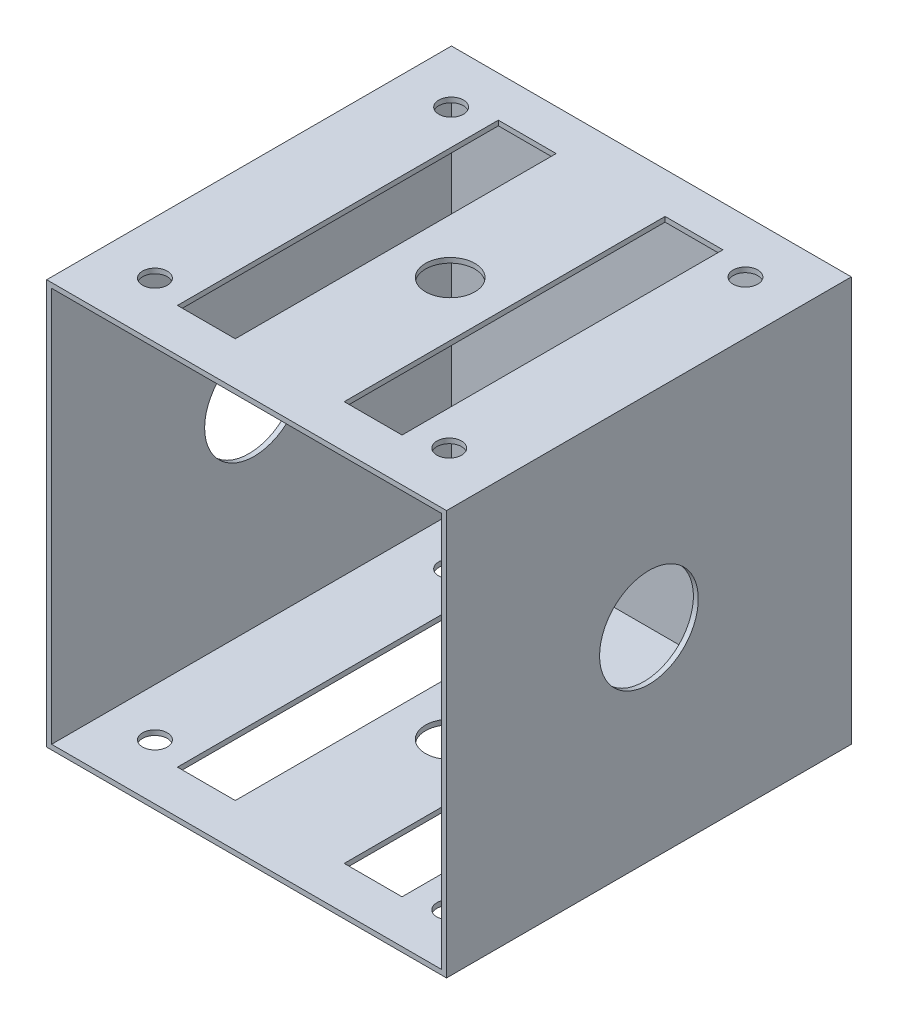
SolidWorks part; units mm, degrees
ref_plane "Front Plane" through (0, 0, 0) normal (0, 0, 1) x (1, 0, 0)
ref_plane "Top Plane" through (0, 0, 0) normal (0, 1, 0) x (1, 0, 0)
ref_plane "Right Plane" through (0, 0, 0) normal (1, 0, 0) x (0, 0, -1)
sketch "Sketch1" plane through (0, 0, 0) normal (0, 0, 1) x (1, 0, 0)
  line L1 (102.87, -104.14) -> (-102.87, -104.14)
  line L2 (102.87, -104.14) -> (102.87, 104.14)
  line L3 (102.87, 104.14) -> (-102.87, 104.14)
  line L4 (-102.87, -104.14) -> (-102.87, 104.14)
  line L5 (102.87, -104.14) -> (-102.87, 104.14) construction
  line L6 (102.87, 104.14) -> (-102.87, -104.14) construction
  point P0 (0, 0)
  dimension "D1" = 205.74
  dimension "D2" = 208.28
extrude "Boss-Extrude1" add sketch "Sketch1" along normal blind 208.28
shell "Shell1" thickness 2.54 removed face at (0, 0, 208.28)
sketch "Sketch2" plane through (0, -101.6, 0) normal (0, 1, 0) x (1, 0, 0)
  line L0 (-102.87, 0) -> (102.87, -207.063) construction
  line L3 (102.87, -208.28) -> (102.87, 0) construction
  line L4 (102.87, 0) -> (-102.87, -208.28) construction
  line L6 (75.7131, -179.7315) -> (-75.7131, -179.7315) construction
  line L7 (75.7131, -179.7315) -> (75.7131, -27.3315) construction
  line L8 (75.7131, -27.3315) -> (-75.7131, -27.3315) construction
  line L9 (-75.7131, -179.7315) -> (-75.7131, -27.3315) construction
  line L10 (75.7131, -179.7315) -> (-75.7131, -27.3315) construction
  line L11 (75.7131, -27.3315) -> (-75.7131, -179.7315) construction
  circle A0 centre (0, -103.5315) radius 12.7
  circle A1 centre (-75.7131, -27.3315) radius 6.35
  circle A2 centre (75.7131, -27.3315) radius 6.35
  circle A3 centre (75.7131, -179.7315) radius 6.35
  circle A4 centre (-75.7131, -179.7315) radius 6.35
  point P3 (102.87, -207.063)
  point P6 (102.87, 0)
  point P21 (-102.87, -208.28)
  point P23 (-102.87, 0)
  point P25 (100.33, -205.1655)
  point P26 (100.33, -208.28)
  dimension "D1" = 25.4
  dimension "D3" = 12.7
  dimension "D2" = 76.2
extrude "Cut-Extrude1" cut sketch "Sketch2" against normal through all both and the other way through all
sketch "Sketch4" plane through (0, 0, 2.54) normal (0, 0, 1) x (1, 0, 0)
  line L0 (-33.02, 0) -> (33.02, 0) construction
  circle A0 centre (0, 0) radius 2.5
  circle A1 centre (33.02, 0) radius 2.5
  circle A2 centre (-33.02, 0) radius 2.5
  point P7 (0, 0)
  point P8 (0, 0)
  point P9 (0, 0)
  point P10 (0, 0)
  point P11 (0, 0)
  dimension "D1" = 5
  dimension "D2" = 33.02
extrude "Cut-Extrude2" cut sketch "Sketch4" against normal blind 208.28
sketch "Sketch5" plane through (0, 104.14, 0) normal (0, 1, 0) x (1, 0, 0)
  line L0 (-42.9007, -103.5315) -> (0, -103.5315) construction
  line L1 (-34.3725, -179.7315) -> (-51.4288, -179.7315)
  line L2 (-34.3725, -179.7315) -> (-34.3725, -27.3315)
  line L3 (-34.3725, -27.3315) -> (-51.4288, -27.3315)
  line L4 (-51.4288, -179.7315) -> (-51.4288, -27.3315)
  line L5 (-34.3725, -179.7315) -> (-51.4288, -27.3315) construction
  line L6 (-34.3725, -27.3315) -> (-51.4288, -179.7315) construction
  line L7 (0, -114.554) -> (0, 114.554) construction
  line L8 (34.3725, -27.3315) -> (51.4288, -27.3315)
  line L9 (51.4288, -179.7315) -> (51.4288, -27.3315)
  line L10 (34.3725, -179.7315) -> (51.4288, -179.7315)
  line L11 (34.3725, -179.7315) -> (34.3725, -27.3315)
  point P0 (-42.9007, -103.5315)
  dimension "D1" = 152.4
extrude "Boss-Extrude2" add sketch "Sketch5" along normal blind 3.175
chamfer "Chamfer1" distance 6.35 angle 45 8 edges at (42.9007, 104.14, 179.7315) (51.4288, 104.14, 103.5315) (42.9007, 104.14, 27.3315) (34.3725, 104.14, 103.5315) (-42.9007, 104.14, 27.3315) (-51.4288, 104.14, 103.5315) (-42.9007, 104.14, 179.7315) (-34.3725, 104.14, 103.5315)
sketch "Sketch6" plane through (0, -104.14, 0) normal (0, -1, 0) x (1, 0, 0)
  line L0 (57.7788, 186.0815) -> (28.0225, 186.0815) construction
  line L1 (57.7788, 20.9815) -> (57.7788, 186.0815) construction
  line L2 (28.0225, 20.9815) -> (57.7788, 20.9815) construction
  line L3 (28.0225, 186.0815) -> (28.0225, 20.9815) construction
  line L12 (-28.0225, 186.0815) -> (-57.7788, 186.0815) construction
  line L13 (-28.0225, 20.9815) -> (-28.0225, 186.0815) construction
  line L14 (-57.7788, 20.9815) -> (-28.0225, 20.9815) construction
  line L15 (-57.7788, 186.0815) -> (-57.7788, 20.9815) construction
  line L16 (57.7788, 186.0815) -> (28.0225, 186.0815)
  line L17 (57.7788, 20.9815) -> (57.7788, 186.0815)
  line L18 (28.0225, 20.9815) -> (57.7788, 20.9815)
  line L19 (28.0225, 186.0815) -> (28.0225, 20.9815)
  line L20 (-28.0225, 186.0815) -> (-57.7788, 186.0815)
  line L21 (-28.0225, 20.9815) -> (-28.0225, 186.0815)
  line L22 (-57.7788, 20.9815) -> (-28.0225, 20.9815)
  line L23 (-57.7788, 186.0815) -> (-57.7788, 20.9815)
extrude "Cut-Extrude3" cut sketch "Sketch6" against normal blind 3.175
sketch "Sketch7" plane through (-102.87, 0, 0) normal (-1, 0, 0) x (0, 0, 1)
  line L0 (0, 104.14) -> (208.28, -104.14) construction
  line L1 (208.28, -104.14) -> (208.28, 104.14) construction
  line L2 (208.28, 104.14) -> (0, -104.14) construction
  circle A0 centre (104.14, 0) radius 25.4
  dimension "D1" = 50.8
extrude "Cut-Extrude4" cut sketch "Sketch7" against normal through all
sketch "Sketch8" plane through (0, 107.315, 0) normal (0, 1, 0) x (1, 0, 0)
  line L0 (28.0225, -20.9815) -> (57.7788, -20.9815) construction
  line L1 (57.7788, -20.9815) -> (57.7788, -186.0815) construction
  line L2 (28.0225, -186.0815) -> (28.0225, -20.9815) construction
  line L3 (57.7788, -186.0815) -> (28.0225, -186.0815) construction
  line L4 (-28.0225, -186.0815) -> (-57.7788, -186.0815) construction
  line L5 (-28.0225, -20.9815) -> (-28.0225, -186.0815) construction
  line L6 (-57.7788, -20.9815) -> (-28.0225, -20.9815) construction
  line L7 (-57.7788, -186.0815) -> (-57.7788, -20.9815) construction
  line L8 (28.0225, -20.9815) -> (57.7788, -20.9815)
  line L9 (57.7788, -20.9815) -> (57.7788, -186.0815)
  line L10 (28.0225, -186.0815) -> (28.0225, -20.9815)
  line L11 (57.7788, -186.0815) -> (28.0225, -186.0815)
  line L12 (-28.0225, -186.0815) -> (-57.7788, -186.0815)
  line L13 (-28.0225, -20.9815) -> (-28.0225, -186.0815)
  line L14 (-57.7788, -20.9815) -> (-28.0225, -20.9815)
  line L15 (-57.7788, -186.0815) -> (-57.7788, -20.9815)
extrude "Cut-Extrude5" cut sketch "Sketch8" against normal through all
